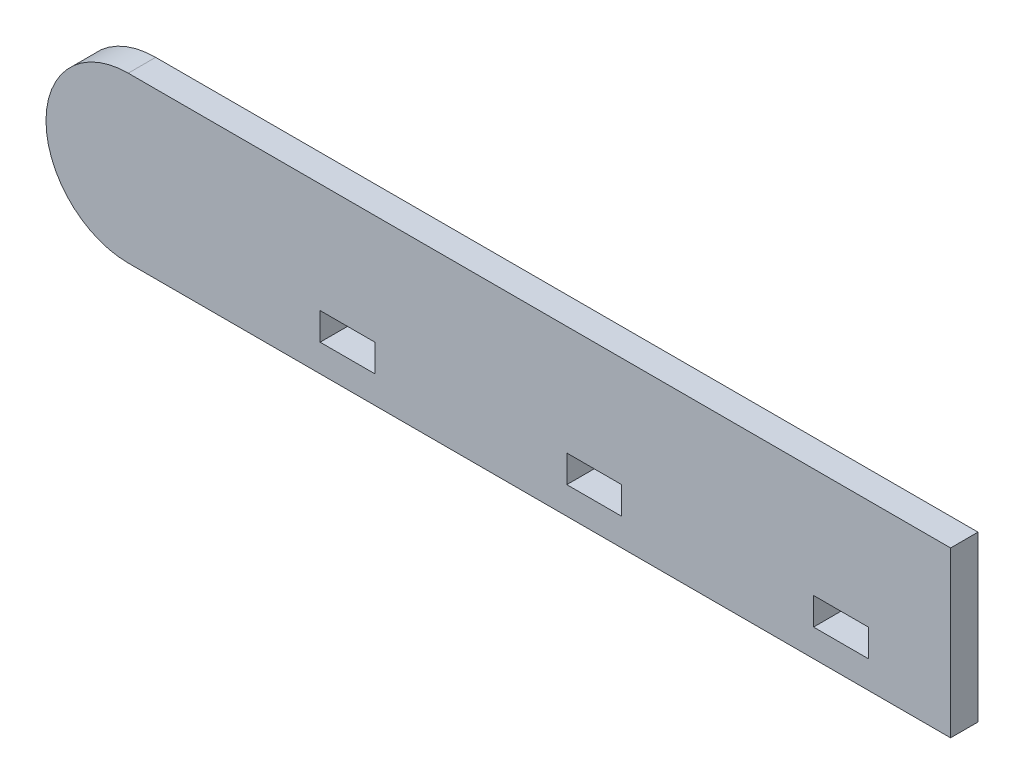
SolidWorks part; units mm, degrees
ref_plane "Plan de face" through (0, 0, 0) normal (0, 0, 1) x (1, 0, 0)
ref_plane "Plan de dessus" through (0, 0, 0) normal (0, 1, 0) x (1, 0, 0)
ref_plane "Plan de droite" through (0, 0, 0) normal (1, 0, 0) x (0, 0, -1)
sketch "Esquisse1" plane through (0, 0, 0) normal (0, 0, 1) x (1, 0, 0)
  line L0 (0, 0) -> (179.4908, 0) construction
  line L2 (0, 15) -> (150, 15)
  line L3 (0, -15) -> (150, -15)
  line L4 (150, 15) -> (150, -15)
  line L5 (35, -5) -> (45, -5)
  line L6 (35, -5) -> (35, -10)
  line L7 (35, -10) -> (45, -10)
  line L8 (45, -5) -> (45, -10)
  line L9 (80, -5) -> (90, -5)
  line L10 (80, -5) -> (80, -10)
  line L11 (80, -10) -> (90, -10)
  line L12 (90, -5) -> (90, -10)
  line L13 (125, -5) -> (135, -5)
  line L14 (125, -5) -> (125, -10)
  line L15 (125, -10) -> (135, -10)
  line L16 (135, -5) -> (135, -10)
  arc A0 (0, 15) -> (0, -15) centre (0, 0) ccw
  line B0 (0, 0) -> (7.25, 0) construction
  line B1 (7.25, 0) -> (7.25, 3.65) construction
  circle B2 centre (0, 0) radius 3.5 construction
  circle B3 centre (7.25, 3.65) radius 0.875 construction
  circle B4 centre (7.25, -3.65) radius 0.875 construction
  circle B5 centre (7.25, -3.65) radius 0.875 construction
  circle B6 centre (3.65, -7.25) radius 0.875 construction
  circle B7 centre (-3.65, -7.25) radius 0.875 construction
  circle B8 centre (-7.25, -3.65) radius 0.875 construction
  circle B9 centre (-7.25, 3.65) radius 0.875 construction
  circle B10 centre (-3.65, 7.25) radius 0.875 construction
  circle B11 centre (3.65, 7.25) radius 0.875 construction
  dimension "D1" = 30
  dimension "D8" = 5
  dimension "D2" = 150
  dimension "D3" = 5
  dimension "D4" = 10
  dimension "D5" = 35
  dimension "D6" = 35
  dimension "D7" = 35
sketch_block_instance "Bloc1-1"
sketch_block "Bloc1" parameters "D3"=1.75, "D1"=7.25, "D2"=3.65
extrude "Boss.-Extru.1" add sketch "Esquisse1" along normal blind 5 contours B2 L6 L5 L8 L10 L9 L12 L14 L13 L16 L4 L2 A0 L3 L15 L11 L7 B9 B8 B4 B3 B6 B7 B10 B11 region at (68.567, 0.2392, 0)
